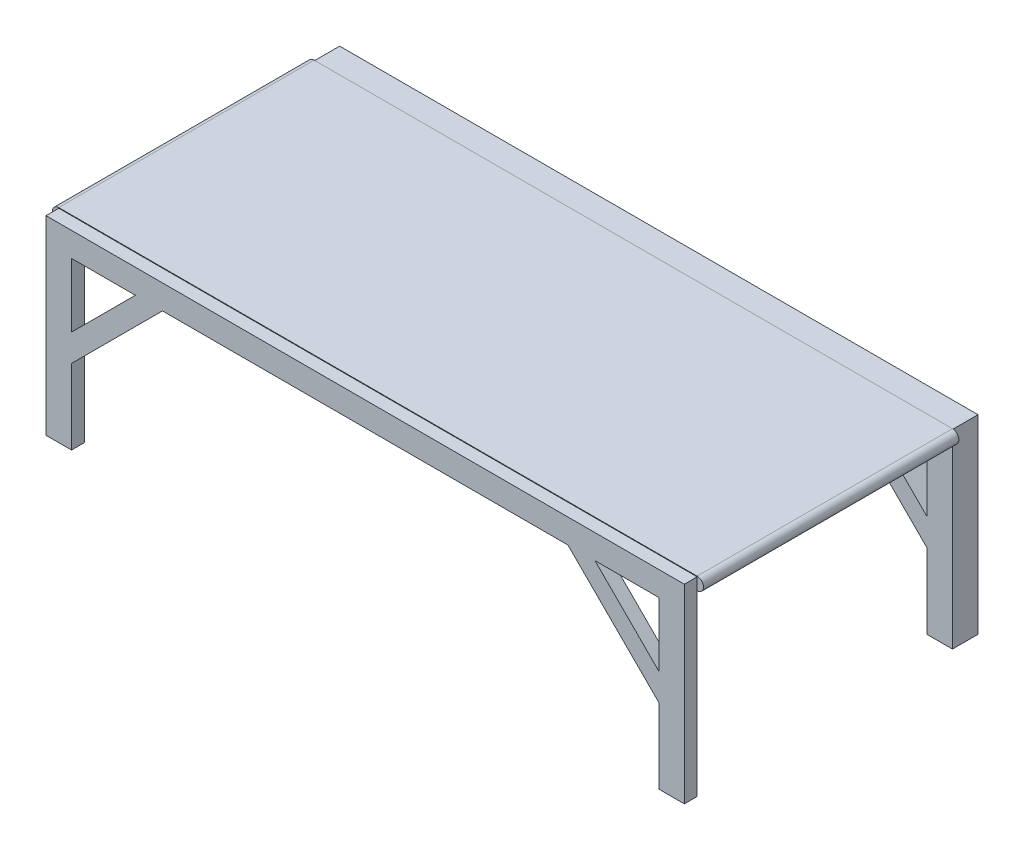
SolidWorks part; units mm, degrees
material "6061 合金"
ref_plane "前视基准面" through (0, 0, 0) normal (0, 0, 1) x (1, 0, 0)
ref_plane "上视基准面" through (0, 0, 0) normal (0, 1, 0) x (1, 0, 0)
ref_plane "右视基准面" through (0, 0, 0) normal (1, 0, 0) x (0, 0, -1)
sketch "草图1" plane through (0, 0, 0) normal (0, 0, 1) x (1, 0, 0)
  line L0 (0, 0) -> (1000, 0) construction
  line L1 (0, 10) -> (1000, 10)
  line L2 (1000, -10) -> (0, -10)
  arc A0 (0, 10) -> (0, -10) centre (0, 0) ccw
  arc A1 (1000, -10) -> (1000, 10) centre (1000, 0) ccw
  dimension "D1" = 20
  dimension "D2" = 1000
extrude "凸台-拉伸1" add sketch "草图1" along normal mid plane 400
sketch "草图2" plane through (0, 0, 200) normal (0, 0, 1) x (1, 0, 0)
  line L0 (0, 0) -> (500, 0) construction
  line L1 (0, -9) -> (1000, -9)
  line L2 (0, -9) -> (0, 9)
  line L3 (0, 9) -> (1000, 9)
  line L4 (1000, -9) -> (1000, 9)
  line L5 (500, 0) -> (500, 10) construction
  line L6 (1000, 10) -> (0, 10) construction
  point P7 (500, 9)
  dimension "D1" = 18
extrude "凸台-拉伸2" add sketch "草图2" along normal blind 20 separate body
sketch "草图3" plane through (0, 0, 220) normal (0, 0, 1) x (1, 0, 0)
  line L0 (0, -9) -> (0, -289)
  line L1 (0, -289) -> (40, -289)
  line L2 (40, -289) -> (40, -171.4264)
  line L3 (40, -171.4264) -> (182.4264, -29)
  line L4 (500, 10) -> (500, 98.6959) construction
  line L5 (1000, 10) -> (0, 10) construction
  line L6 (960, -171.4264) -> (817.5736, -29)
  line L7 (960, -289) -> (960, -171.4264)
  line L8 (1000, -289) -> (960, -289)
  line L9 (1000, -9) -> (1000, -289)
  line L10 (182.4264, -29) -> (817.5736, -29)
  line L11 (0, -9) -> (1000, -9)
  line L12 (40, -29) -> (40, -129)
  line L13 (40, -129) -> (140, -29)
  line L14 (140, -29) -> (40, -29)
  line L15 (960, -129) -> (860, -29)
  line L16 (960, -29) -> (960, -129)
  line L17 (860, -29) -> (960, -29)
  dimension "D1" = 280
  dimension "D2" = 20
  dimension "D3" = 30
  dimension "D4" = 135
  dimension "D5" = 40
  dimension "D6" = 100
extrude "凸台-拉伸3" add sketch "草图3" against normal up to surface (20 mm away) up to face at (500, 0, 200)
extrude "凸台-拉伸4" add sketch "草图2<2>" against normal blind 40 from surface separate body starting at face at (500, 0, -200)
sketch "草图2<2>" plane through (0, 0, 200) normal (0, 0, 1) x (1, 0, 0) same geometry as "草图2"
extrude "凸台-拉伸5" add sketch "草图3<2>" along normal blind 40 from surface starting at face at (500, 0, -240)
sketch "草图3<2>" plane through (0, 0, 220) normal (0, 0, 1) x (1, 0, 0) same geometry as "草图3"
